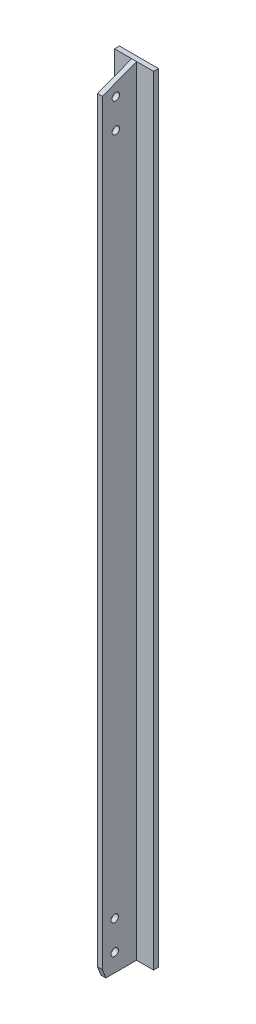
SolidWorks part; units mm, degrees
material "6061-T6 (SS)"
ref_plane "Front Plane" through (0, 0, 0) normal (0, 0, 1) x (1, 0, 0)
ref_plane "Top Plane" through (0, 0, 0) normal (0, 1, 0) x (1, 0, 0)
ref_plane "Right Plane" through (0, 0, 0) normal (1, 0, 0) x (0, 0, -1)
sketch "Sketch2" plane through (0, 0, 0) normal (0, 1, 0) x (1, 0, 0)
  line L1 (0, 0) -> (3.175, 0)
  line L2 (0, 0) -> (0, 22.225)
  line L4 (3.175, 0) -> (3.175, 22.225)
  line L7 (14.2875, 22.225) -> (3.175, 22.225)
  line L8 (14.2875, 22.225) -> (14.2875, 25.4)
  line L9 (14.2875, 25.4) -> (-11.1125, 25.4)
  line L10 (-11.1125, 22.225) -> (-11.1125, 25.4)
  line L14 (0, 22.225) -> (-11.1125, 22.225)
  point P0 (0, 0)
  point P3 (0, 0)
  dimension "D1" = 25.4
  dimension "D2" = 25.4
  dimension "D3" = 3.175
  dimension "D4" = 3.175
extrude "Boss-Extrude1" add sketch "Sketch2" along normal blind 558.8
sketch "Sketch4" plane through (3.175, 0, 0) normal (1, 0, 0) x (0, 0, -1)
  line L5 (22.225, 0) -> (0, 57.8981)
  line L6 (0, 558.8) -> (0, 0) construction
  line L7 (0, 57.8981) -> (0, 0)
  line L8 (0, 0) -> (22.225, 0)
  line L9 (22.225, 558.8) -> (0, 550.2686)
  line L10 (0, 550.2686) -> (0, 558.8)
  line L11 (0, 558.8) -> (22.225, 558.8)
  dimension "D1" = 21
  dimension "D2" = 69
extrude "Cut-Extrude1" cut sketch "Sketch4" against normal blind 438.15
sketch "Sketch5" plane through (3.175, 0, 0) normal (1, 0, 0) x (0, 0, -1)
  line L0 (25.4, 0) -> (25.4, 52.07)
  line L2 (25.4, 558.8) -> (25.4, 0) construction
  line L3 (25.4, 52.07) -> (-7.4795, 52.07)
  line L4 (-7.4795, 52.07) -> (-7.4795, 0)
  line L5 (-7.4795, 0) -> (25.4, 0)
  dimension "D1" = 52.07
extrude "Cut-Extrude2" cut sketch "Sketch5" against normal through all both and the other way through all
sketch "Sketch6" plane through (3.175, 0, 0) normal (1, 0, 0) x (0, 0, -1)
  line L0 (22.225, 558.8) -> (22.225, 52.07) construction
  line L1 (2.2372, 52.07) -> (22.225, 52.07) construction
  line L2 (8.001, 63.754) -> (8.001, 82.804) construction
  line L4 (0, 550.2686) -> (0, 57.8981) construction
  circle A0 centre (8.001, 63.754) radius 2.413
  circle A1 centre (8.001, 82.804) radius 2.413
  dimension "D1" = 14.224
  dimension "D2" = 11.684
  dimension "D4" = 4.826
  dimension "D5" = 4.826
  dimension "D3" = 19.05
extrude "Cut-Extrude3" cut sketch "Sketch6" against normal through all
sketch "Sketch7" plane through (3.175, 0, 0) normal (1, 0, 0) x (0, 0, -1)
  line L0 (0, 550.2686) -> (22.225, 558.8) construction
  line L1 (22.225, 558.8) -> (22.225, 52.07) construction
  line L2 (8.763, 526.6974) -> (8.763, 545.7474) construction
  circle A0 centre (8.763, 526.6974) radius 2.413
  circle A2 centre (8.763, 545.7474) radius 2.413
  dimension "D1" = 4.826
  dimension "D2" = 25.146
  dimension "D3" = 13.462
  dimension "D5" = 4.826
  dimension "D4" = 19.05
extrude "Cut-Extrude4" cut sketch "Sketch7" against normal through all
